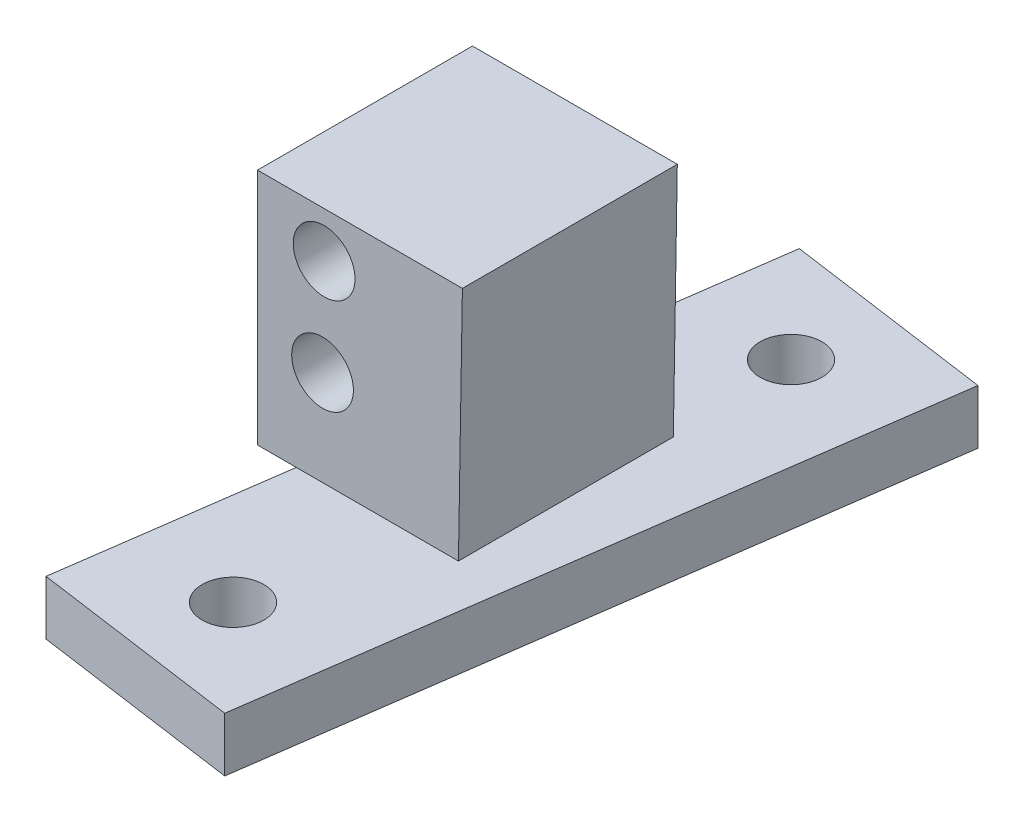
SolidWorks part; units mm, degrees
ref_plane "Front Plane" through (0, 0, 0) normal (0, 0, 1) x (1, 0, 0)
ref_plane "Top Plane" through (0, 0, 0) normal (0, 1, 0) x (1, 0, 0)
ref_plane "Right Plane" through (0, 0, 0) normal (1, 0, 0) x (0, 0, -1)
sketch "Sketch1" plane through (0, 0, 0) normal (0, 0, 1) x (1, 0, 0)
  line L0 (430.4818, 135.1883) -> (451.5463, 135.1883)
  line L1 (426.8731, 135.2483) -> (443.5981, 134.9701) construction
  line L2 (451.5463, 135.1883) -> (451.1391, 110.7021)
  line L3 (451.1391, 110.7021) -> (430.4818, 110.7021)
  line L4 (430.4818, 110.7021) -> (430.4818, 135.1883)
  line L5 (427.9702, 112.9511) -> (437.0368, 112.8004) construction
  line L6 (427.9702, 112.9511) -> (437.0368, 112.8004)
  line L7 (427.9702, 112.9511) -> (437.0368, 112.8004)
  line L8 (427.9702, 112.9511) -> (437.0368, 112.8004)
  line L9 (427.9702, 112.9511) -> (437.0368, 112.8004)
  line L10 (427.9702, 112.9511) -> (437.0368, 112.8004)
  arc A0 (444.3649, 127.3721) -> (443.5981, 134.9701) centre (437.3311, 130.5) ccw construction
  arc A1 (444.3649, 127.3721) -> (444.2998, 123.3969) centre (449.0067, 125.308) ccw construction
  arc A2 (443.2811, 115.8212) -> (444.2998, 123.3969) centre (437.1648, 120.5) ccw construction
  arc A3 (441.8282, 114.3719) -> (443.2811, 115.8212) centre (437.1648, 120.5) ccw construction
  arc A4 (437.0368, 112.8004) -> (441.8282, 114.3719) centre (437.1648, 120.5) ccw construction
  arc A5 (444.3649, 127.3721) -> (443.5981, 134.9701) centre (437.3311, 130.5) ccw
  arc A6 (444.3649, 127.3721) -> (444.2998, 123.3969) centre (449.0067, 125.308) ccw
  arc A7 (443.2811, 115.8212) -> (444.2998, 123.3969) centre (437.1648, 120.5) ccw
  arc A8 (441.8282, 114.3719) -> (443.2811, 115.8212) centre (437.1648, 120.5) ccw
  arc A9 (437.0368, 112.8004) -> (441.8282, 114.3719) centre (437.1648, 120.5) ccw
  circle A10 centre (437.3311, 130.5) radius 3.175
  circle A11 centre (437.1648, 120.5) radius 3.175
extrude "Boss-Extrude1" add sketch "Sketch1" along normal up to surface (22.098 mm away) contours L4 L3 L2 L0 A11 A10 region at (441.4313, 122.629, 0)
ref_plane "Plane1" through (0, 110.7021, 0) normal (0, 1, 0) x (1, 0, 0)
sketch "Sketch2" plane through (0, 110.7021, 0) normal (0, 1, 0) x (1, 0, 0)
  line L0 (431.2956, -44.663) -> (440.8401, 23.2496)
  line L1 (440.8401, 23.2496) -> (462.22, 20.2449)
  line L2 (462.22, 20.2449) -> (452.6755, -47.6677)
  line L3 (452.6755, -47.6677) -> (431.2956, -44.663)
  line L4 (430.4818, -22.098) -> (451.1391, -22.098) construction
  circle A0 centre (443.2228, -37.3619) radius 3.175
  circle A1 centre (450.2928, 12.9438) radius 3.175
  dimension "D5" = 8.89
  dimension "D9" = 6.35
  dimension "D10" = 6.35
  dimension "D1" = 21.59
  dimension "D2" = 68.58
  dimension "D3" = 21.59
  dimension "D4" = 5.08
  dimension "D6" = 8.89
  dimension "D7" = 10.795
  dimension "D8" = 10.795
  dimension "D11" = 98
extrude "Boss-Extrude2" add sketch "Sketch2" against normal blind 5.588
